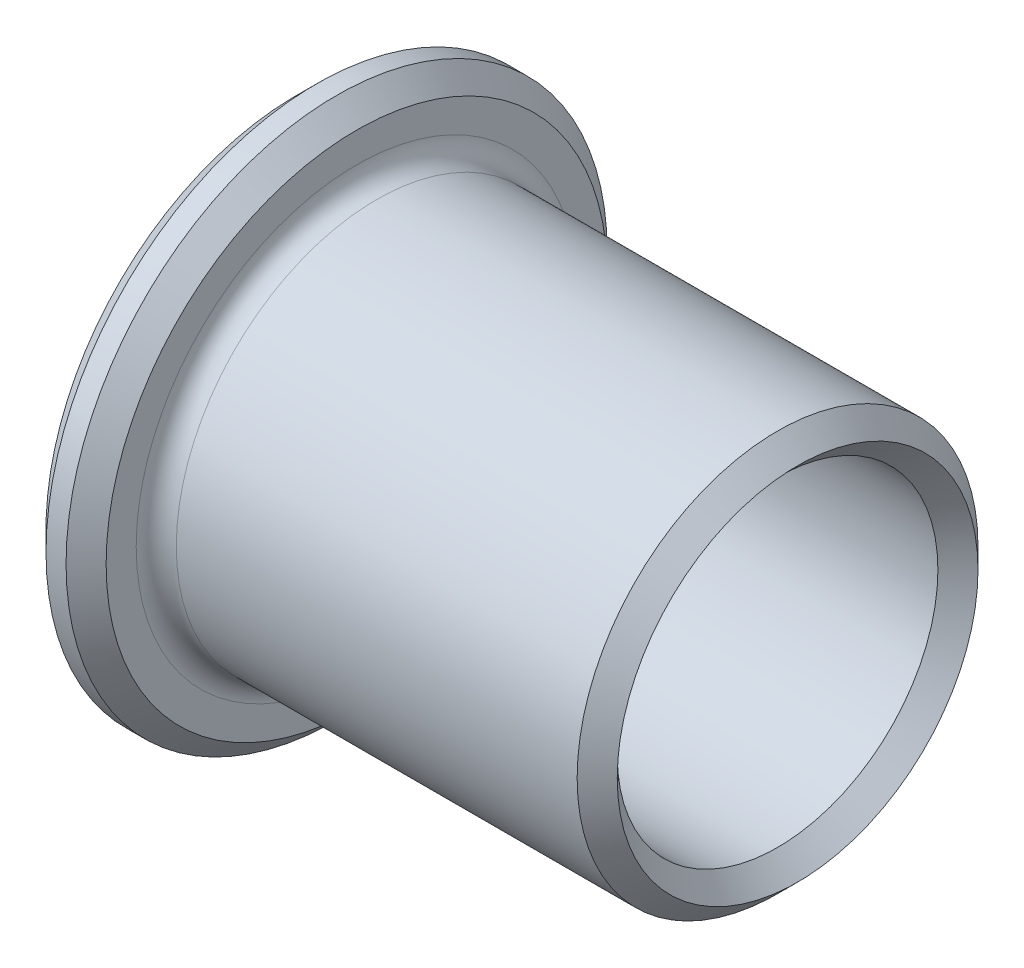
SolidWorks part; units mm, degrees
material "Phosphor bronze 10% D, UNS C52400"
ref_plane "Front Plane" through (0, 0, 0) normal (0, 0, 1) x (1, 0, 0)
ref_plane "Top Plane" through (0, 0, 0) normal (0, 1, 0) x (1, 0, 0)
ref_plane "Right Plane" through (0, 0, 0) normal (1, 0, 0) x (0, 0, -1)
sketch "Sketch1" plane through (0, 0, 0) normal (0, 0, 1) x (1, 0, 0)
  line L0 (0, 8) -> (25, 8)
  line L1 (25, 8) -> (25, 10)
  line L2 (25, 10) -> (3, 10)
  line L3 (3, 10) -> (3, 13.5)
  line L4 (3, 13.5) -> (0, 13.5)
  line L5 (0, 13.5) -> (0, 8)
  line L6 (0, 0) -> (44.8454, 0) construction
  dimension "D1" = 16
  dimension "D2" = 3
  dimension "D3" = 27
  dimension "D4" = 25
  dimension "D5" = 20
revolve "Revolve1" add sketch "Sketch1" angle 360 about L6
chamfer "Chamfer1" distance 1 angle 45 5 edges at (0, 0, 8) (25, 0, 8) (3, 0, 13.5) (0, 0, 13.5) (25, 0, 10)
fillet "Fillet1" radius 1 1 edges at (3, 0, 10)
